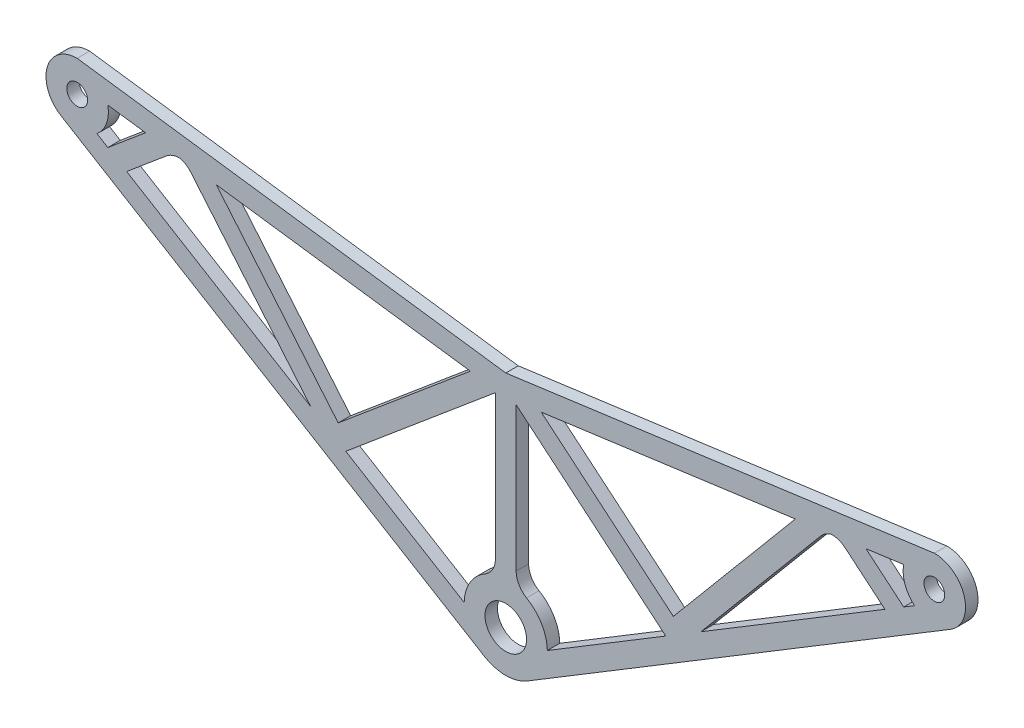
SolidWorks part; units mm, degrees
ref_plane "前视基准面" through (0, 0, 0) normal (0, 0, 1) x (1, 0, 0)
ref_plane "上视基准面" through (0, 0, 0) normal (0, 1, 0) x (1, 0, 0)
ref_plane "右视基准面" through (0, 0, 0) normal (1, 0, 0) x (0, 0, -1)
sketch "草图1" plane through (0, 0, 0) normal (0, 0, 1) x (1, 0, 0)
  line L0 (0, 53) -> (0, -10) construction
  line L1 (0, 0) -> (103.057, 59.5) construction
  line L2 (0, 53) -> (-103.057, 67)
  line L3 (0, 0) -> (-103.057, 59.5) construction
  line L4 (0, 53) -> (103.057, 67)
  line L5 (-106.9426, 53.085) -> (-5.1808, -8.5533)
  line L6 (5.1808, -8.5533) -> (106.9426, 53.085)
  line L7 (0, 53) -> (-40.6004, 18.9323) construction
  line L8 (0, 53) -> (40.6004, 18.9323) construction
  line L9 (-40.6004, 18.9323) -> (-78.0878, 63.608) construction
  line L10 (40.6004, 18.9323) -> (78.0878, 63.608) construction
  line L11 (-78.0878, 63.608) -> (-93.1067, 51.0056) construction
  line L12 (78.0878, 63.608) -> (93.1067, 51.0056) construction
  line L13 (-8.523, 49.1119) -> (-69.6256, 57.4125)
  line L14 (46.9198, 22.5742) -> (91.1632, 49.3729)
  line L15 (-98.3041, 53.6983) -> (-95.6807, 52.1092)
  line L16 (9.9978, 0.2101) -> (38.4702, 17.4562)
  line L17 (-8.523, 49.1119) -> (-40.2922, 22.4543)
  line L18 (-40.2922, 22.4543) -> (-69.6256, 57.4125)
  line L19 (-86.6107, 59.7199) -> (-95.6807, 52.1092)
  line L20 (-2.5, 47.6387) -> (-38.4702, 17.4562)
  line L21 (-46.9198, 22.5742) -> (-76.9924, 58.4133)
  line L22 (-79.916, 58.8104) -> (-91.1632, 49.3729)
  line L23 (2.5, 47.6387) -> (38.4702, 17.4562)
  line L24 (46.9198, 22.5742) -> (76.9924, 58.4133)
  line L25 (79.916, 58.8104) -> (91.1632, 49.3729)
  line L26 (8.523, 49.1119) -> (40.2922, 22.4543)
  line L27 (40.2922, 22.4543) -> (69.6256, 57.4125)
  line L28 (86.6107, 59.7199) -> (95.6807, 52.1092)
  line L29 (-38.4702, 17.4562) -> (-9.9978, 0.2101)
  line L30 (-2.5, 47.6387) -> (-2.5, 9.6825)
  line L31 (2.5, 47.6387) -> (2.5, 9.6825)
  line L32 (77.7796, 67.1301) -> (94.7136, 52.9207) construction
  line L33 (-1.607, 54.9151) -> (-40.2922, 22.4543) construction
  line L34 (1.607, 54.9151) -> (40.2922, 22.4543) construction
  line L35 (1.607, 51.0849) -> (-40.9085, 15.4102) construction
  line L36 (-1.607, 51.0849) -> (40.9085, 15.4102) construction
  line L37 (-2.5, 53) -> (-2.5, -10) construction
  line L38 (2.5, 53) -> (2.5, -10) construction
  line L39 (-40.2922, 22.4543) -> (-77.7796, 67.1301) construction
  line L40 (-77.7796, 67.1301) -> (-94.7136, 52.9207) construction
  line L41 (-40.9085, 15.4102) -> (-78.3959, 60.0859) construction
  line L42 (-78.3959, 60.0859) -> (-91.4997, 49.0905) construction
  line L43 (40.9085, 15.4102) -> (78.3959, 60.0859) construction
  line L44 (2.5, -9.6825) -> (2.5, -10)
  line L45 (40.2922, 22.4543) -> (77.7796, 67.1301) construction
  line L46 (78.3959, 60.0859) -> (91.4997, 49.0905) construction
  line L47 (-2.5, -9.6825) -> (-2.5, -10)
  line L48 (102.1548, 61.8315) -> (103.7301, 62.0455)
  line L49 (-104.3522, 57.3617) -> (-2.5904, -4.2767) construction
  line L50 (2.5904, -4.2767) -> (104.3522, 57.3617) construction
  line L51 (86.6107, 59.7199) -> (95.6994, 60.9546)
  line L52 (95.6807, 52.1092) -> (98.3041, 53.6983)
  line L53 (76.9924, 58.4133) -> (79.916, 58.8104)
  line L54 (8.523, 49.1119) -> (69.6256, 57.4125)
  line L55 (-76.9924, 58.4133) -> (-79.916, 58.8104)
  line L56 (-86.6107, 59.7199) -> (-95.6994, 60.9546)
  line L57 (-91.1632, 49.3729) -> (-46.9198, 22.5742)
  line L58 (-102.1548, 61.8315) -> (-103.7301, 62.0455)
  arc A0 (-2.5, 9.6825) -> (-9.9978, 0.2101) centre (0, 0) ccw
  arc A1 (-98.3041, 53.6983) -> (-95.6994, 60.9546) centre (-103.057, 59.5) ccw
  arc A2 (106.9426, 53.085) -> (101.0562, 66.7282) centre (103.057, 59.5) ccw
  circle A3 centre (0, 0) radius 5
  circle A4 centre (-103.057, 59.5) radius 2.5
  circle A5 centre (103.057, 59.5) radius 2.5
  arc A6 (-5.1808, -8.5533) -> (5.1808, -8.5533) centre (0, 0) ccw
  arc A7 (9.9978, 0.2101) -> (2.5, 9.6825) centre (0, 0) ccw
  arc A8 (95.6994, 60.9546) -> (98.3041, 53.6983) centre (103.057, 59.5) ccw
  arc A9 (-101.0562, 66.7282) -> (-106.9426, 53.085) centre (-103.057, 59.5) ccw
  point P5 (0, 53)
  dimension "D1" = 10
  dimension "D2" = 20
  dimension "D3" = 5
  dimension "D4" = 15
  dimension "D5" = 5
  dimension "D6" = 15
  dimension "D7" = 60
  dimension "D8" = 60
  dimension "D9" = 119
  dimension "D10" = 119
  dimension "D11" = 53
  dimension "D12" = 53
  dimension "D13" = 53
  dimension "D23" = 5
  dimension "D15" = 5
  dimension "D24" = 5
  dimension "D25" = 5
  dimension "D26" = 50
  dimension "D27" = 50
  dimension "D14" = 2.5
  dimension "D16" = 5
  dimension "D17" = 5
  dimension "D18" = 2.5
  dimension "D19" = 2.5
  dimension "D20" = 2.5
  dimension "D21" = 2.5
  dimension "D22" = 2.5
extrude "凸台-拉伸1" add sketch "草图1" along normal blind 3 contours L2 A9 L5 A6 L6 A2 L4 L51 A8 L52 L28 L16 A7 L31 L23 L15 A1 L56 L19 L30 A0 L29 L20 L26 L54 L27 L24 L53 L25 L14 L17 L18 L13 L57 L22 L55 L21 A3 region at (0, 38.3719, 0)
fillet "圆角1" radius 5 2 edges at (76.9924, 58.4133, 1.5) (79.916, 58.8104, 1.5)
fillet "圆角2" radius 5 2 edges at (-79.916, 58.8104, 1.5) (-76.9924, 58.4133, 1.5)
fillet "圆角3" radius 5 2 edges at (-2.5, 9.6825, 1.5) (2.5, 9.6825, 1.5)
